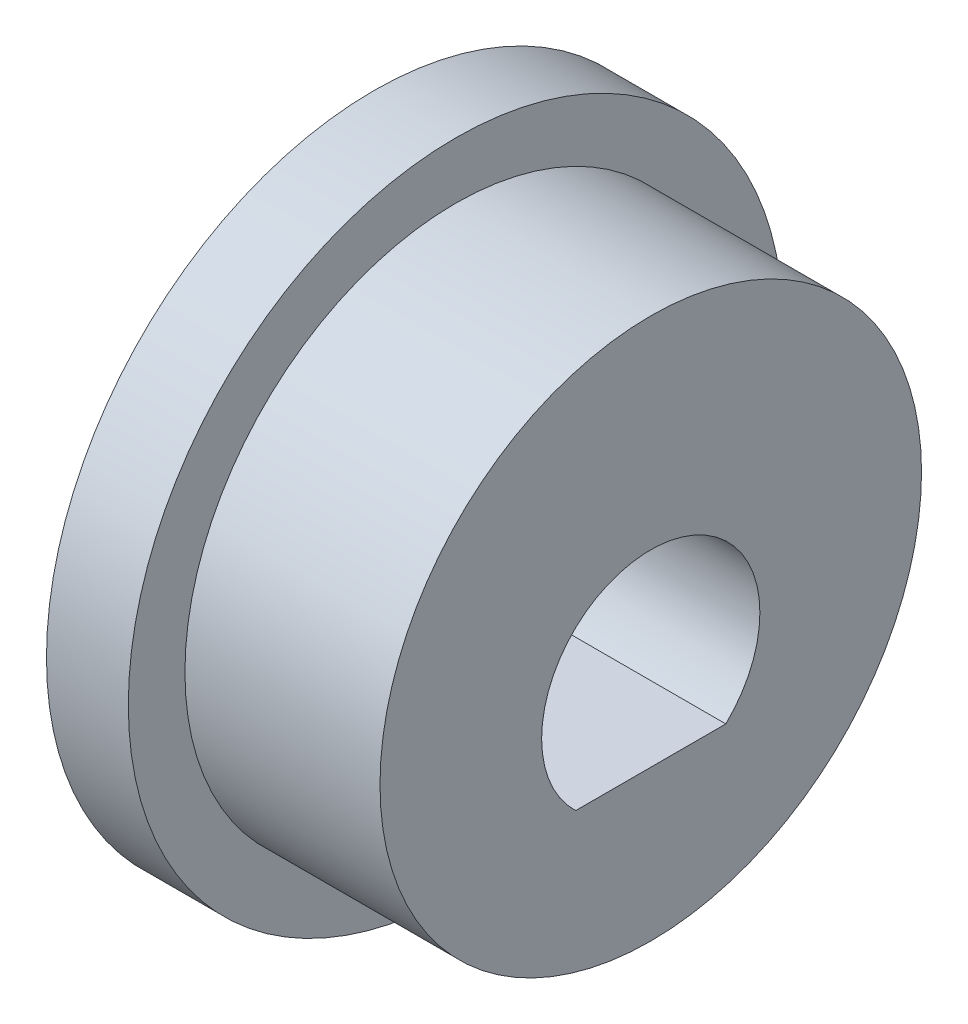
SolidWorks part; units mm, degrees
ref_plane "Ebene vorne" through (0, 0, 0) normal (0, 0, 1) x (1, 0, 0)
ref_plane "Ebene oben" through (0, 0, 0) normal (0, 1, 0) x (1, 0, 0)
ref_plane "Ebene rechts" through (0, 0, 0) normal (1, 0, 0) x (0, 0, -1)
sketch "Skizze1" plane through (0, 0, 0) normal (1, 0, 0) x (0, 0, -1)
  circle A0 centre (0, 1.5) radius 9.925
  dimension "D1" = 19.85
  dimension "D2" = 1.5
extrude "Aufsatz-Linear austragen1" add sketch "Skizze1" along normal blind 7.15
sketch "Skizze2" plane through (0, 0, 0) normal (-1, 0, 0) x (0, 0, 1)
  circle A0 centre (0, 1.5) radius 12
  dimension "D1" = 24
extrude "Aufsatz-Linear austragen2" add sketch "Skizze2" along normal blind 3
sketch "Skizze3" plane through (7.15, 0, 0) normal (1, 0, 0) x (0, 0, -1)
  line L0 (2.75, -2.9047) -> (-2.75, -2.9047)
  arc A0 (2.75, -2.9047) -> (-2.75, -2.9047) centre (0, 0) ccw
  dimension "D1" = 4
  dimension "D2" = 5.5
extrude "Schnitt-Linear austragen1" cut sketch "Skizze3" against normal through all and the other way through all
